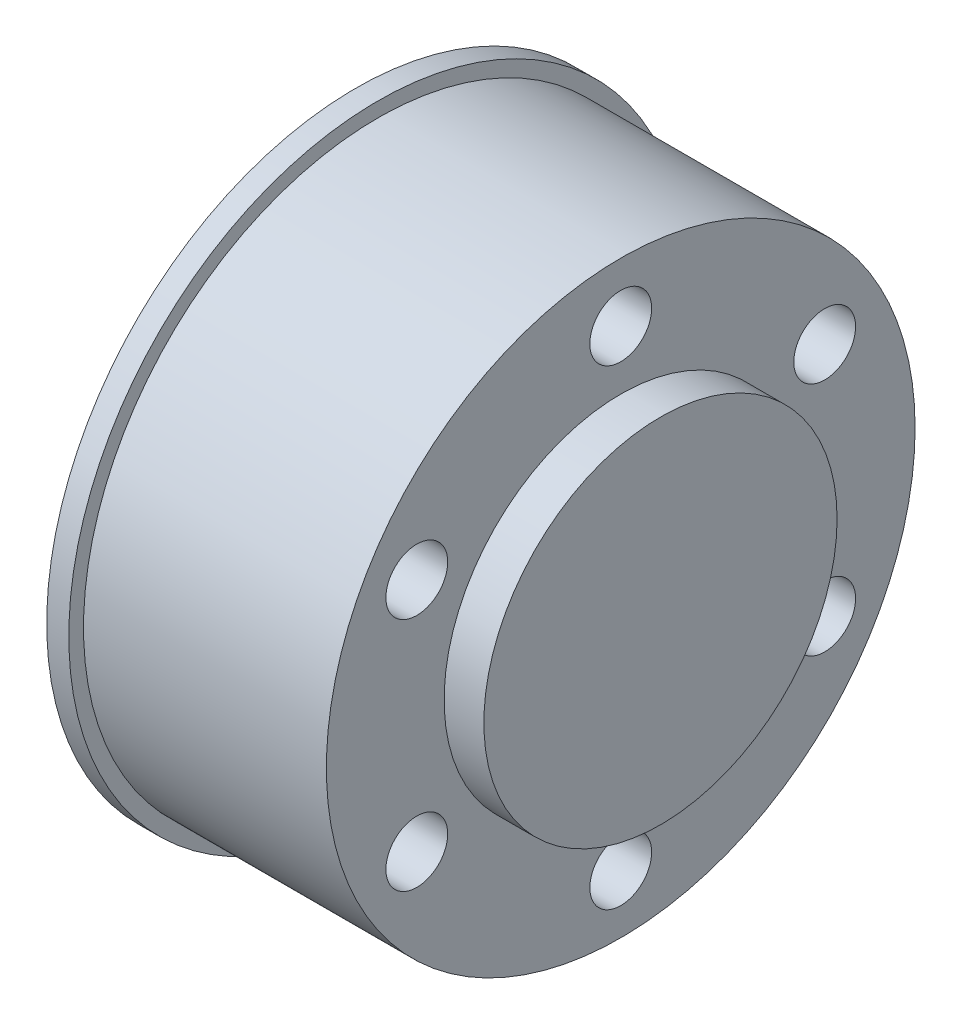
SolidWorks part; units mm, degrees
ref_plane "Front Plane" through (0, 0, 0) normal (0, 0, 1) x (1, 0, 0)
ref_plane "Top Plane" through (0, 0, 0) normal (0, 1, 0) x (1, 0, 0)
ref_plane "Right Plane" through (0, 0, 0) normal (1, 0, 0) x (0, 0, -1)
sketch "Sketch2" plane through (0, 0, 0) normal (0, 1, 0) x (1, 0, 0)
  line L0 (0, 0) -> (0, 12)
  line L1 (0, 12) -> (-2.7, 12)
  line L2 (-2.7, 12) -> (-2.7, 20)
  line L3 (-2.7, 20) -> (-19.2, 20)
  line L4 (-19.2, 20) -> (-19.2, 21)
  line L5 (-19.2, 21) -> (-20.7, 21)
  line L6 (-20.7, 21) -> (-20.7, 17.6528)
  line L7 (0, 0) -> (-41.2311, 0) construction
  line L11 (-20.7, 14.5) -> (-20.7, 8)
  line L12 (-20.7, 8) -> (-15.7, 8)
  line L13 (-15.7, 8) -> (-15.7, 6)
  line L14 (-15.7, 6) -> (-14.7, 6)
  line L15 (-14.7, 6) -> (-14.7, 0)
  line L16 (-14.7, 0) -> (0, 0)
  line L17 (-20.7, 17.6528) -> (-20.7, 14.5)
  dimension "D1" = 12
  dimension "D2" = 2.7
  dimension "D3" = 8
  dimension "D4" = 16.5
  dimension "D5" = 1
  dimension "D6" = 1.5
  dimension "D8" = 8
  dimension "D9" = 6
  dimension "D10" = 5
  dimension "D13" = 1
revolve "Revolve1" add sketch "Sketch2" angle 360 about L7
sketch "Sketch3" plane through (-20.7, 0, 0) normal (-1, 0, 0) x (0, 0, 1)
  circle A0 centre (0, 16) radius 1.5
  circle A1 centre (13.8564, 7.9047) radius 1.5
  circle A2 centre (13.7739, -8.1429) radius 1.5
  circle A3 centre (-0.165, -16.0953) radius 1.5
  circle A4 centre (-14.0214, -8) radius 1.5
  circle A5 centre (-13.9389, 8.0476) radius 1.5
  dimension "D1" = 3
  dimension "D3" = 16
  dimension "D2" = 6
extrude "Cut-Extrude1" cut sketch "Sketch3" against normal blind 4
sketch "Sketch4" plane through (-2.7, 0, 0) normal (1, 0, 0) x (0, 0, -1)
  circle A0 centre (0, 16) radius 2.1
  circle A1 centre (13.8564, 8) radius 2.1
  circle A2 centre (13.8564, -8) radius 2.1
  circle A3 centre (0, -16) radius 2.1
  circle A4 centre (-13.8564, -8) radius 2.1
  circle A5 centre (-13.8564, 8) radius 2.1
  point P15 (0, 0)
  dimension "D1" = 4.2
  dimension "D2" = 16
  dimension "D3" = 6
extrude "Cut-Extrude2" cut sketch "Sketch4" against normal blind 10
sketch "Sketch5" plane through (-2.7, 0, 0) normal (1, 0, 0) x (0, 0, -1)
  line L1 (10, 17.3205) -> (-10, -17.3205) construction
  circle A0 centre (0, 0) radius 20 construction
  circle A1 centre (0, 0) radius 20 construction
  point P9 (8.8264, 17.947)
